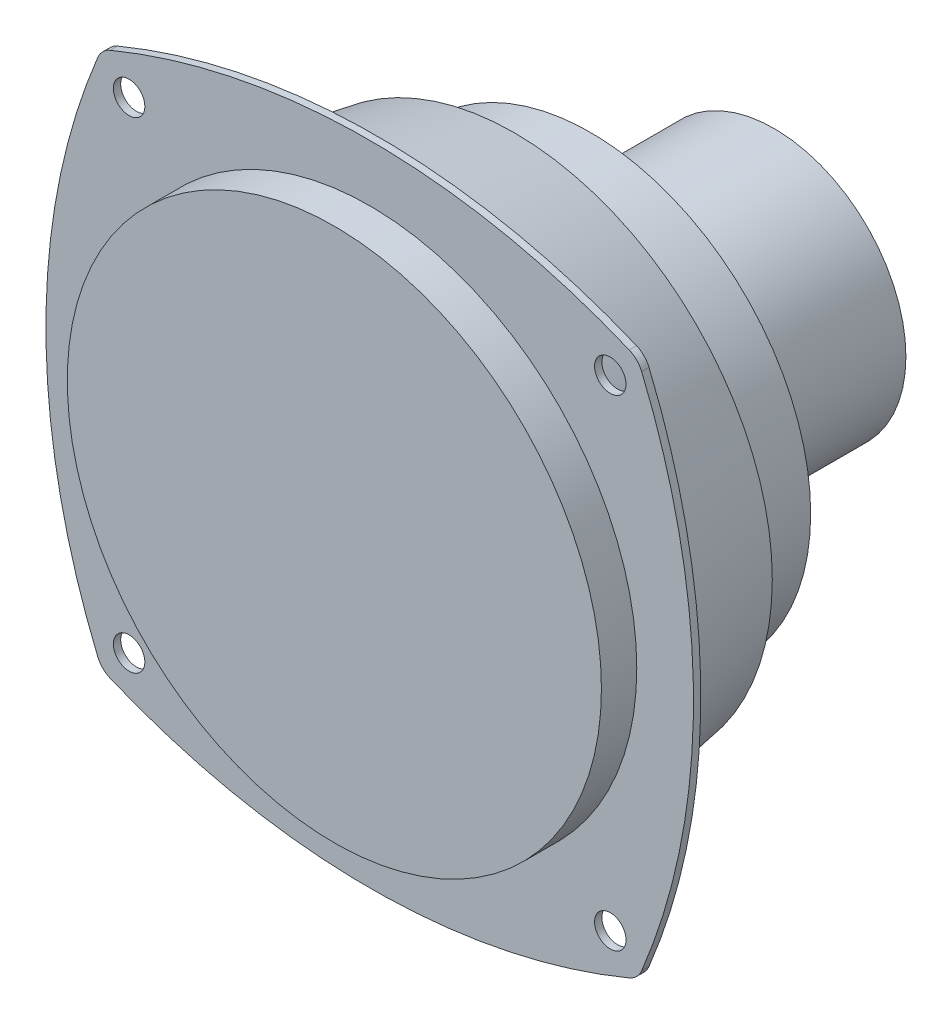
SolidWorks part; units mm, degrees
ref_plane "Front Plane" through (0, 0, 0) normal (0, 0, 1) x (1, 0, 0)
ref_plane "Top Plane" through (0, 0, 0) normal (0, 1, 0) x (1, 0, 0)
ref_plane "Right Plane" through (0, 0, 0) normal (1, 0, 0) x (0, 0, -1)
sketch "Sketch1" plane through (0, 0, 0) normal (1, 0, 0) x (0, 0, -1)
  line L0 (0, 0) -> (60.11, 0) construction
  line L1 (60.11, 0) -> (60.11, 18)
  line L2 (60.11, 18) -> (35.01, 18)
  line L3 (35.01, 18) -> (35.01, 30.085)
  line L4 (35.01, 30.085) -> (24.6, 30.085)
  line L5 (5.83, 38.44) -> (5.83, 44.25)
  line L6 (5.83, 44.25) -> (4.83, 44.25)
  line L7 (4.83, 44.25) -> (4.83, 36.5)
  line L8 (4.83, 36.5) -> (0, 36.5)
  line L9 (0, 36.5) -> (0, 0)
  line L10 (0, 0) -> (60.11, 0)
  line L11 (24.6, 35.25) -> (5.83, 38.44)
  line L12 (24.6, 30.085) -> (24.6, 35.25)
  dimension "D1" = 25.1
  dimension "D2" = 10.41
  dimension "D3" = 88.5
  dimension "D4" = 36
  dimension "D5" = 73
  dimension "D6" = 4.83
  dimension "D7" = 1
  dimension "D8" = 38.44
  dimension "D9" = 35.25
  dimension "D10" = 30.085
  dimension "D11" = 18.77
revolve "Revolve1" add sketch "Sketch1" angle 360 about L0
sketch "Sketch2" plane through (0, 0, -4.83) normal (0, 0, 1) x (1, 0, 0)
  line L0 (-36.4823, 36.4823) -> (36.4823, -36.4823) construction
  line L1 (-34.2372, -37.4122) -> (34.2372, -37.4122) construction
  line L2 (-37.4122, -34.2372) -> (-37.4122, 34.2372) construction
  line L3 (-34.2372, 37.4122) -> (34.2372, 37.4122) construction
  line L4 (37.4122, -34.2372) -> (37.4122, 34.2372) construction
  line L5 (0, 37.4122) -> (0, -37.4122) construction
  line L6 (-37.4122, 0) -> (37.4122, 0) construction
  arc A0 (34.2372, 37.4122) -> (37.4122, 34.2372) centre (34.2372, 34.2372) cw construction
  arc A1 (34.2372, -37.4122) -> (37.4122, -34.2372) centre (34.2372, -34.2372) ccw construction
  arc A2 (-34.2372, -37.4122) -> (-37.4122, -34.2372) centre (-34.2372, -34.2372) cw construction
  arc A3 (-37.4122, 34.2372) -> (-34.2372, 37.4122) centre (-34.2372, 34.2372) cw construction
  arc A4 (-35.4568, 37.1687) -> (35.4568, 37.1687) centre (0, -48.058) cw
  arc A6 (37.1687, 35.4568) -> (37.1687, -35.4568) centre (-48.058, 0) cw
  arc A7 (35.4568, -37.1687) -> (-35.4568, -37.1687) centre (0, 48.058) cw
  arc A8 (-37.1687, -35.4568) -> (-37.1687, 35.4568) centre (48.058, 0) cw
  arc A9 (-37.1687, 35.4568) -> (-35.4568, 37.1687) centre (-34.2372, 34.2372) cw
  arc A10 (35.4568, 37.1687) -> (37.1687, 35.4568) centre (34.2372, 34.2372) cw
  arc A11 (35.4568, -37.1687) -> (37.1687, -35.4568) centre (34.2372, -34.2372) ccw
  arc A12 (-37.1687, -35.4568) -> (-35.4568, -37.1687) centre (-34.2372, -34.2372) ccw
  circle A13 centre (0, 0) radius 44.25 construction
  point P0 (0, 0)
  point P32 (0, 0)
  dimension "D1" = 103.1875
  dimension "D2" = 3.175
extrude "Boss-Extrude1" add sketch "Sketch2" against normal up to surface (1 mm away) up to face at (44.25, 0, -5.83)
hole_wizard "Ø4.3 (4.3) Diameter Hole1" positions "Sketch4" profile "Sketch5" hole size "Ø4.3" standard "ANSI Metric" end condition through all
sketch "Sketch4" plane through (0, 0, -4.83) normal (0, 0, 1) x (1, 0, 0)
  line L0 (-32.8805, -32.8805) -> (32.8805, 32.8805) construction
  line L3 (-32.8805, 32.8805) -> (32.8805, -32.8805) construction
  circle A0 centre (0, 0) radius 46.5
  point P0 (-32.8805, 32.8805)
  point P7 (32.8805, 32.8805)
  point P9 (32.8805, -32.8805)
  point P11 (-32.8805, -32.8805)
  dimension "D1" = 93
sketch "Sketch5" plane through (-32.8805, 32.8805, -4.83) normal (1, 0, 0) x (0, -1, 0)
  line L0 (0, 0) -> (0, 55.28)
  line L1 (0, 55.28) -> (2.15, 55.28)
  line L2 (2.15, 55.28) -> (2.15, 0)
  line L5 (2.15, 0) -> (0, 0)
  line L11 (0, -6.35) -> (0, 107.95) construction
  dimension "Thru Hole Dia." = 4.3
  dimension "Thru Hole Depth" = 55.28
sketch "Sketch6" plane through (0, 0, -5.83) normal (0, 0, -1) x (-1, 0, 0)
  line L0 (0, -37.35) -> (0, 0) construction
  line L1 (-14.085, -37.35) -> (14.085, -37.35)
  line L2 (-14.085, -37.35) -> (-14.085, -39.85)
  line L3 (-14.085, -39.85) -> (14.085, -39.85)
  line L4 (14.085, -37.35) -> (14.085, -39.85)
  line L5 (0, -39.85) -> (0, -37.35) construction
  line L6 (-14.085, -38.6) -> (14.085, -38.6) construction
  arc A0 (-35.4568, -37.1687) -> (35.4568, -37.1687) centre (0, 48.058) ccw construction
  point P8 (0, -44.25)
  point P88 (0, -38.6)
  dimension "D1" = 28.17
  dimension "D2" = 4.4
  dimension "D3" = 2.5
extrude "Boss-Extrude2" add sketch "Sketch6" along normal blind 23.53
